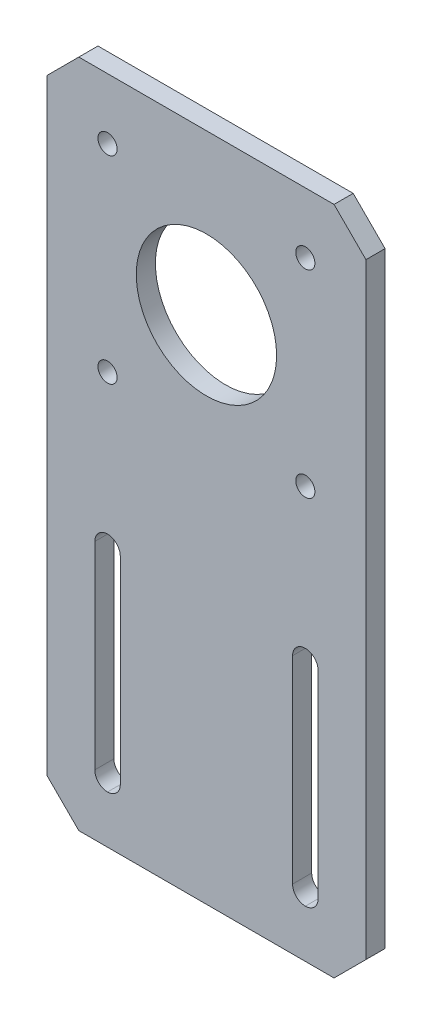
SolidWorks part; units mm, degrees
ref_plane "前视基准面" through (0, 0, 0) normal (0, 0, 1) x (1, 0, 0)
ref_plane "上视基准面" through (0, 0, 0) normal (0, 1, 0) x (1, 0, 0)
ref_plane "右视基准面" through (0, 0, 0) normal (1, 0, 0) x (0, 0, -1)
sketch "草图1" plane through (0, 0, 0) normal (0, 0, 1) x (1, 0, 0)
  line L0 (-20, 25) -> (-25, 20)
  line L5 (-20, 25) -> (20, 25)
  line L17 (-25, 20) -> (-25, -75)
  line L18 (-20, -80) -> (20, -80)
  line L19 (20, 25) -> (25, 20)
  line L22 (25, -75) -> (25, 20)
  line L23 (-20, -80) -> (-25, -75)
  line L24 (20, -80) -> (25, -75)
  line L29 (-17.5, -37.5) -> (-17.5, -72.5)
  line L30 (-17.5, -72.5) -> (-13.5, -72.5)
  line L31 (17.5, -72.5) -> (17.5, -37.5)
  line L32 (17.5, -37.5) -> (13.5, -37.5)
  line L37 (-13.5, -37.5) -> (-13.5, -72.5)
  line L38 (13.5, -37.5) -> (13.5, -72.5)
  line L39 (-13.5, -37.5) -> (-17.5, -37.5)
  line L40 (13.5, -72.5) -> (17.5, -72.5)
  circle A0 centre (-15.5, 15.5) radius 1.5
  circle A1 centre (15.5, 15.5) radius 1.5
  circle A2 centre (15.5, -15.5) radius 1.5
  circle A3 centre (-15.5, -15.5) radius 1.5
  dimension "D1" = 4
extrude "凸台-拉伸1" add sketch "草图1" along normal blind 3
fillet "圆角1" radius 2 8 edges at (17.5, -72.5, 1.5) (-13.5, -72.5, 1.5) (13.5, -37.5, 1.5) (-17.5, -37.5, 1.5) (-17.5, -72.5, 1.5) (13.5, -72.5, 1.5) (17.5, -37.5, 1.5) (-13.5, -37.5, 1.5)
sketch "草图2" plane through (0, 0, 3) normal (0, 0, 1) x (1, 0, 0)
  circle A0 centre (0, 0) radius 11
extrude "切除-拉伸1" cut sketch "草图2" against normal blind 3
